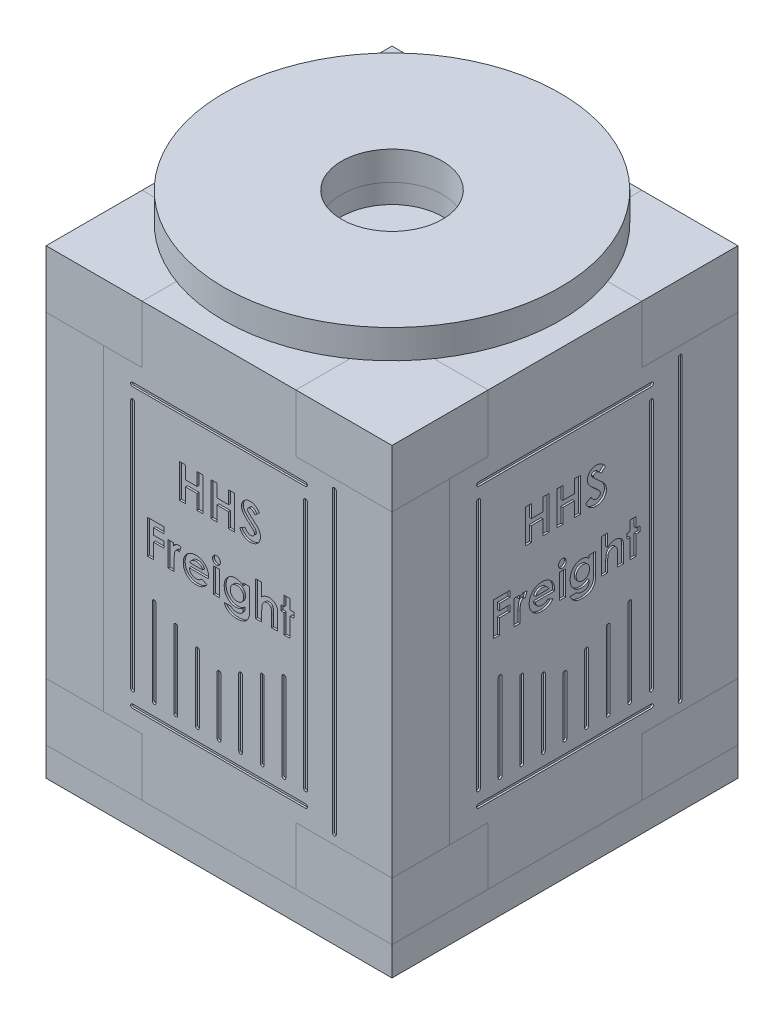
SolidWorks part; units mm, degrees
material "Cedar"
ref_plane "Front Plane" through (0, 0, 0) normal (0, 0, 1) x (1, 0, 0)
ref_plane "Top Plane" through (0, 0, 0) normal (0, 1, 0) x (1, 0, 0)
ref_plane "Right Plane" through (0, 0, 0) normal (1, 0, 0) x (0, 0, -1)
sketch "Sketch1" plane through (0, 0, 0) normal (0, 1, 0) x (1, 0, 0)
  line L0 (18, 8) -> (12, 8)
  line L1 (-18, -18) -> (18, -18)
  line L2 (-18, -18) -> (-18, 18)
  line L3 (-18, 18) -> (18, 18)
  line L4 (18, -18) -> (18, 18)
  line L5 (-18, -18) -> (18, 18) construction
  line L6 (-18, 18) -> (18, -18) construction
  line L7 (-8, 18) -> (8, 18)
  line L8 (-8, 18) -> (-8, 12)
  line L9 (-8, 12) -> (8, 12)
  line L10 (8, 18) -> (8, 12)
  line L11 (12, -8) -> (12, 8)
  line L12 (18, -8) -> (12, -8)
  line L13 (18, -8) -> (18, 8)
  line L14 (8, -18) -> (-8, -18)
  line L15 (8, -18) -> (8, -12)
  line L16 (8, -12) -> (-8, -12)
  line L17 (-8, -18) -> (-8, -12)
  line L18 (-18, -8) -> (-12, -8)
  line L19 (-12, 8) -> (-12, -8)
  line L20 (-18, 8) -> (-12, 8)
  line L21 (-18, 8) -> (-18, -8)
  circle A0 centre (0, 0) radius 16
  circle A1 centre (0, 0) radius 5.25
  dimension "D2" = 32
  dimension "D3" = 10.5
  dimension "D1" = 36
  dimension "D4" = 10
  dimension "D5" = 10
  dimension "D6" = 6
extrude "Boss-Extrude1" add sketch "Sketch1" along normal blind 6 contours A0 L9 L8 L3 L2 L20 L19 | A0 L19 L18 L2 L1 L17 L16 | L16 A0 L11 L9 L19 A1 | A0 L16 L15 L1 L4 L12 L11 | A0 L11 L0 L4 L3 L10 L9 | A1 region at (13.7273, 0, -13.7273) region at (12.9282, 0, -8.3919) region at (13.7273, 0, 13.7273) region at (-13.7273, 0, -13.7273) region at (-13.7273, 0, 13.7273) region at (0, 0, 0)
extrude "Boss-Extrude2" add sketch "Sketch1<3>" along normal blind 2 from offset 6 separate body contours A0 | A1
sketch "Sketch1<3>" plane through (0, 0, 0) normal (0, 1, 0) x (1, 0, 0) same geometry as "Sketch1"
sketch "Sketch2" plane through (0, 0, 12) normal (0, 0, 1) x (1, 0, 0)
  line L0 (8, 0) -> (18, 0) construction
  line L1 (18, 0) -> (18, 6) construction
  line L2 (18, 6) -> (8, 6) construction
  line L3 (8, 6) -> (8, 0) construction
  line L4 (-18, 0) -> (-8, 0) construction
  line L5 (-8, 0) -> (-8, 6) construction
  line L6 (-8, 6) -> (-18, 6) construction
  line L7 (-18, 6) -> (-18, 0) construction
  line L8 (8, 0) -> (18, 0)
  line L9 (18, 0) -> (18, 6)
  line L10 (18, 6) -> (8, 6)
  line L11 (8, 6) -> (8, 0)
  line L12 (-18, 0) -> (-8, 0)
  line L13 (-8, 0) -> (-8, 6)
  line L14 (-8, 6) -> (-18, 6)
  line L15 (-18, 6) -> (-18, 0)
  line L16 (-8, 6) -> (8, 6)
  line L17 (-12, 0) -> (-12, -33)
  line L18 (-12, -16.5) -> (18, -16.5) construction
  line L19 (18, 0) -> (18, -33)
  line L20 (-8, -39) -> (8, -39)
  line L21 (-18, -39) -> (-18, -33)
  line L22 (-8, -39) -> (-18, -39)
  line L23 (-8, -33) -> (-8, -39)
  line L24 (-18, -33) -> (-8, -33)
  line L25 (8, -39) -> (8, -33)
  line L26 (18, -39) -> (8, -39)
  line L27 (18, -33) -> (18, -39)
  line L28 (8, -33) -> (18, -33)
  line L29 (16, 8) -> (-16, 8) construction
  line M5 (-8, 0) -> (8, 0)
  line M6 (8, 0) -> (8, 6)
  line M8 (-8, 6) -> (-8, 0)
  dimension "D1" = 6
  dimension "D2" = 47
extrude "Boss-Extrude3" add sketch "Sketch2" along normal blind 6 separate body contours L18 L17 L24 L23 L20 L25 L28 L19 | L17 L18 L19 L8 L12 M5 | M8 M5 M6 region at (0, 3, 12) region at (3, -8.25, 12) region at (2.5127, -26.5774, 12)
sketch "Sketch4" plane through (0, 0, 18) normal (0, 0, 1) x (1, 0, 0)
  line L0 (12, -1) -> (12, -32) construction
  line L1 (-12, -33) -> (-8, -33) construction
  line L2 (-12, 0) -> (-8, 0) construction
  line L3 (12.2, -1) -> (12.2, -32)
  line L4 (11.8, -1) -> (11.8, -32)
  line L5 (-9, -2) -> (9, -2) construction
  line L6 (-9, -1.8) -> (9, -1.8)
  line L7 (-9, -2.2) -> (9, -2.2)
  line L8 (-9, -3.5) -> (-9, -29.5) construction
  line L9 (-8.8, -3.5) -> (-8.8, -29.5)
  line L10 (-9.2, -3.5) -> (-9.2, -29.5)
  line L11 (9, -3.5) -> (9, -29.5) construction
  line L12 (9.2, -3.5) -> (9.2, -29.5)
  line L13 (8.8, -3.5) -> (8.8, -29.5)
  line L14 (-9, -31) -> (9, -31) construction
  line L15 (-9, -30.8) -> (9, -30.8)
  line L16 (-9, -31.2) -> (9, -31.2)
  line L17 (-4.5, -21.5) -> (-4.5, -29.5) construction
  line L18 (-4.3, -21.5) -> (-4.3, -29.5)
  line L19 (-4.7, -21.5) -> (-4.7, -29.5)
  line L20 (0, -23.5) -> (0, -29.5) construction
  line L21 (0.2, -23.5) -> (0.2, -29.5)
  line L22 (-0.2, -23.5) -> (-0.2, -29.5)
  line L23 (4.5, -21.5) -> (4.5, -29.5) construction
  line L24 (4.7, -21.5) -> (4.7, -29.5)
  line L25 (4.3, -21.5) -> (4.3, -29.5)
  line L26 (-8.8, -10) -> (8.8, -10) construction
  line L27 (18, 0) -> (18, -33) construction
  line L28 (8, -33) -> (18, -33) construction
  line L29 (8, 0) -> (18, 0) construction
  line L30 (-12, 0) -> (-12, -33) construction
  line L31 (-9, -29.5) -> (-4.5, -29.5) construction
  line L32 (-4.5, -29.5) -> (0, -29.5) construction
  line L33 (0, -29.5) -> (4.5, -29.5) construction
  line L34 (4.5, -29.5) -> (9, -29.5) construction
  line L35 (-6.75, -29.5) -> (-6.75, -20.5) construction
  line L36 (-6.95, -29.5) -> (-6.95, -20.5)
  line L37 (-6.55, -29.5) -> (-6.55, -20.5)
  line L38 (-2.25, -29.5) -> (-2.25, -22.5) construction
  line L39 (-2.45, -29.5) -> (-2.45, -22.5)
  line L40 (-2.05, -29.5) -> (-2.05, -22.5)
  line L41 (2.25, -29.5) -> (2.25, -22.5) construction
  line L42 (2.05, -29.5) -> (2.05, -22.5)
  line L43 (2.45, -29.5) -> (2.45, -22.5)
  line L44 (6.75, -29.5) -> (6.75, -20.5) construction
  line L45 (6.55, -29.5) -> (6.55, -20.5)
  line L46 (6.95, -29.5) -> (6.95, -20.5)
  line L47 (-4.1282, -6.5) -> (-3.5, -6.5)
  line L48 (-3.5, -6.5) -> (-3.5, -7.8462)
  line L49 (-3.5, -7.8462) -> (-2.2885, -7.8462)
  line L50 (-2.2885, -7.8462) -> (-2.2885, -6.5)
  line L51 (-2.2885, -6.5) -> (-1.6603, -6.5)
  line L52 (-1.6603, -6.5) -> (-1.6603, -10)
  line L53 (-1.6603, -10) -> (-2.2885, -10)
  line L54 (-2.2885, -10) -> (-2.2885, -8.4744)
  line L55 (-2.2885, -8.4744) -> (-3.5, -8.4744)
  line L56 (-3.5, -8.4744) -> (-3.5, -10)
  line L57 (-3.5, -10) -> (-4.1282, -10)
  line L58 (-4.1282, -10) -> (-4.1282, -6.5)
  line L59 (-0.8526, -6.5) -> (-0.2244, -6.5)
  line L60 (-0.2244, -6.5) -> (-0.2244, -7.8462)
  line L61 (-0.2244, -7.8462) -> (0.9872, -7.8462)
  line L62 (0.9872, -7.8462) -> (0.9872, -6.5)
  line L63 (0.9872, -6.5) -> (1.6154, -6.5)
  line L64 (1.6154, -6.5) -> (1.6154, -10)
  line L65 (1.6154, -10) -> (0.9872, -10)
  line L66 (0.9872, -10) -> (0.9872, -8.4744)
  line L67 (0.9872, -8.4744) -> (-0.2244, -8.4744)
  line L68 (-0.2244, -8.4744) -> (-0.2244, -10)
  line L69 (-0.2244, -10) -> (-0.8526, -10)
  line L70 (-0.8526, -10) -> (-0.8526, -6.5)
  line L71 (4.2179, -6.9676) -> (3.7482, -7.3974)
  line L72 (2.1538, -9.3445) -> (2.7063, -9.0128)
  line L73 (-7.4487, -13.1987) -> (-5.7436, -13.1987)
  line L74 (-5.7436, -13.1987) -> (-5.7436, -13.8269)
  line L75 (-5.7436, -13.8269) -> (-6.8205, -13.8269)
  line L76 (-6.8205, -13.8269) -> (-6.8205, -14.5)
  line L77 (-6.8205, -14.5) -> (-5.7436, -14.5)
  line L78 (-5.7436, -14.5) -> (-5.7436, -15.1282)
  line L79 (-5.7436, -15.1282) -> (-6.8205, -15.1282)
  line L80 (-6.8205, -15.1282) -> (-6.8205, -16.6987)
  line L81 (-6.8205, -16.6987) -> (-7.4487, -16.6987)
  line L82 (-7.4487, -16.6987) -> (-7.4487, -13.1987)
  line L83 (-5.2949, -14.141) -> (-4.7564, -14.141)
  line L84 (-4.7564, -14.141) -> (-4.7564, -14.4558)
  line L85 (-3.9487, -14.1593) -> (-4.1436, -14.6914)
  line L86 (-4.6688, -15.5384) -> (-4.6667, -15.6632)
  line L87 (-4.6667, -15.6632) -> (-4.6667, -16.6987)
  line L88 (-4.6667, -16.6987) -> (-5.2949, -16.6987)
  line L89 (-5.2949, -16.6987) -> (-5.2949, -14.141)
  line L90 (-1.079, -15.5769) -> (-3.0962, -15.5769)
  line L91 (-1.7823, -15.9394) -> (-1.2564, -16.1897)
  line L92 (-1.0769, -15.4584) -> (-1.079, -15.5769)
  line L93 (-3.0513, -15.0833) -> (-1.7051, -15.0833)
  line L94 (-0.5833, -14.141) -> (0.0449, -14.141)
  line L95 (0.0449, -14.141) -> (0.0449, -16.6987)
  line L96 (0.0449, -16.6987) -> (-0.5833, -16.6987)
  line L97 (-0.5833, -16.6987) -> (-0.5833, -14.141)
  line L98 (2.5128, -14.141) -> (3.1859, -14.141)
  line L99 (3.1859, -14.141) -> (3.1859, -16.3229)
  line L100 (0.5357, -16.8782) -> (1.234, -16.8782)
  line L101 (2.5128, -14.4257) -> (2.5128, -14.141)
  line L102 (3.8141, -13.109) -> (4.4423, -13.109)
  line L103 (4.4423, -13.109) -> (4.4423, -14.418)
  line L104 (6.1026, -15.0216) -> (6.1026, -16.6987)
  line L105 (6.1026, -16.6987) -> (5.4744, -16.6987)
  line L106 (5.4744, -16.6987) -> (5.4744, -15.5867)
  line L107 (4.4423, -15.68) -> (4.4423, -16.6987)
  line L108 (4.4423, -16.6987) -> (3.8141, -16.6987)
  line L109 (3.8141, -16.6987) -> (3.8141, -13.109)
  line L110 (6.7756, -13.109) -> (7.4038, -13.109)
  line L111 (7.4038, -13.109) -> (7.4038, -14.141)
  line L112 (7.4038, -14.141) -> (7.8077, -14.141)
  line L113 (7.8077, -14.141) -> (7.8077, -14.6795)
  line L114 (7.8077, -14.6795) -> (7.4038, -14.6795)
  line L115 (7.4038, -14.6795) -> (7.4038, -16.6987)
  line L116 (7.4038, -16.6987) -> (6.7756, -16.6987)
  line L117 (6.7756, -16.6987) -> (6.7756, -14.6795)
  line L118 (6.7756, -14.6795) -> (6.4615, -14.6795)
  line L119 (6.4615, -14.6795) -> (6.4615, -14.141)
  line L120 (6.4615, -14.141) -> (6.7756, -14.141)
  line L121 (6.7756, -14.141) -> (6.7756, -13.109)
  arc A0 (12.2, -1) -> (11.8, -1) centre (12, -1) ccw
  arc A1 (11.8, -32) -> (12.2, -32) centre (12, -32) ccw
  arc A2 (-9, -1.8) -> (-9, -2.2) centre (-9, -2) ccw
  arc A3 (9, -2.2) -> (9, -1.8) centre (9, -2) ccw
  arc A4 (-8.8, -3.5) -> (-9.2, -3.5) centre (-9, -3.5) ccw
  arc A5 (-9.2, -29.5) -> (-8.8, -29.5) centre (-9, -29.5) ccw
  arc A6 (9.2, -3.5) -> (8.8, -3.5) centre (9, -3.5) ccw
  arc A7 (8.8, -29.5) -> (9.2, -29.5) centre (9, -29.5) ccw
  arc A8 (-9, -30.8) -> (-9, -31.2) centre (-9, -31) ccw
  arc A9 (9, -31.2) -> (9, -30.8) centre (9, -31) ccw
  arc A10 (-4.3, -21.5) -> (-4.7, -21.5) centre (-4.5, -21.5) ccw
  arc A11 (-4.7, -29.5) -> (-4.3, -29.5) centre (-4.5, -29.5) ccw
  arc A12 (0.2, -23.5) -> (-0.2, -23.5) centre (0, -23.5) ccw
  arc A13 (-0.2, -29.5) -> (0.2, -29.5) centre (0, -29.5) ccw
  arc A14 (4.7, -21.5) -> (4.3, -21.5) centre (4.5, -21.5) ccw
  arc A15 (4.3, -29.5) -> (4.7, -29.5) centre (4.5, -29.5) ccw
  arc A16 (-6.95, -29.5) -> (-6.55, -29.5) centre (-6.75, -29.5) ccw
  arc A17 (-6.55, -20.5) -> (-6.95, -20.5) centre (-6.75, -20.5) ccw
  arc A18 (-2.45, -29.5) -> (-2.05, -29.5) centre (-2.25, -29.5) ccw
  arc A19 (-2.05, -22.5) -> (-2.45, -22.5) centre (-2.25, -22.5) ccw
  arc A20 (2.05, -29.5) -> (2.45, -29.5) centre (2.25, -29.5) ccw
  arc A21 (2.45, -22.5) -> (2.05, -22.5) centre (2.25, -22.5) ccw
  arc A22 (6.55, -29.5) -> (6.95, -29.5) centre (6.75, -29.5) ccw
  arc A23 (6.95, -20.5) -> (6.55, -20.5) centre (6.75, -20.5) ccw
  spline S0 degree 3 poles (3.7482, -7.3974) (3.7106, -7.3423) (3.6515, -7.2661) (3.5645, -7.1794) (3.5019, -7.1281) (3.4384, -7.0881) (3.3546, -7.0509) (3.2883, -7.0383) (3.2448, -7.0385) knots 0 0 0 0 0.311824 0.448433 0.573381 0.689077 0.797573 1 1 1 1
  spline S1 degree 3 poles (3.2448, -7.0385) (3.2066, -7.0384) (3.1496, -7.0452) (3.0828, -7.0771) (3.0402, -7.1074) (3.0066, -7.1439) (2.9712, -7.194) (2.9619, -7.2389) (2.9615, -7.2677) knots 0 0 0 0 0.285993 0.416634 0.54738 0.671583 0.784401 1 1 1 1
  spline S2 degree 3 poles (2.9615, -7.2677) (2.9611, -7.2971) (2.9723, -7.3571) (3.0015, -7.4105) (3.0197, -7.4353) knots 0 0 0 0 0.487115 1 1 1 1
  spline S3 degree 3 poles (3.0197, -7.4353) (3.0376, -7.4592) (3.0725, -7.4967) (3.126, -7.5513) (3.1811, -7.6035) (3.2447, -7.6643) (3.3507, -7.7592) (3.435, -7.8345) (3.4951, -7.8868) knots 0 0 0 0 0.136349 0.233805 0.349411 0.483179 0.635967 1 1 1 1
  spline S4 degree 3 poles (3.4951, -7.8868) (3.5508, -7.9353) (3.6307, -8.0035) (3.7298, -8.091) (3.791, -8.145) (3.8427, -8.1917) (3.8936, -8.2392) (3.927, -8.2713) (3.9459, -8.2907) knots 0 0 0 0 0.366184 0.520457 0.655012 0.770624 0.865677 1 1 1 1
  spline S5 degree 3 poles (3.9459, -8.2907) (4.0062, -8.354) (4.0886, -8.4498) (4.1769, -8.5853) (4.2261, -8.682) (4.2632, -8.7795) (4.2987, -8.9155) (4.3078, -9.0218) (4.3077, -9.0934) knots 0 0 0 0 0.289954 0.417139 0.535255 0.648751 0.762405 1 1 1 1
  spline S6 degree 3 poles (4.3077, -9.0934) (4.3088, -9.1629) (4.2986, -9.2651) (4.2693, -9.3968) (4.2361, -9.4885) (4.1957, -9.5763) (4.1449, -9.6588) (4.0854, -9.7369) (4.0171, -9.8091) (3.9416, -9.8747) (3.8606, -9.933) (3.7733, -9.9812) (3.6805, -10.0209) (3.5823, -10.0514) (3.4413, -10.0823) (3.3313, -10.0899) (3.2567, -10.0897) knots 0 0 0 0 0.127927 0.189047 0.248544 0.307607 0.367248 0.426963 0.488617 0.550392 0.611331 0.672556 0.734024 0.797341 0.86225 1 1 1 1
  spline S7 degree 3 poles (3.2567, -10.0897) (3.1974, -10.0897) (3.1097, -10.0845) (2.9957, -10.0657) (2.9145, -10.0459) (2.8359, -10.0207) (2.7601, -9.9899) (2.6875, -9.9531) (2.6177, -9.9111) (2.5509, -9.8622) (2.4863, -9.8075) (2.4245, -9.7463) (2.3653, -9.6785) (2.309, -9.6041) (2.2337, -9.495) (2.1853, -9.4058) (2.1538, -9.3445) knots 0 0 0 0 0.125868 0.18624 0.244977 0.303358 0.36123 0.418489 0.475937 0.534204 0.594059 0.655469 0.718772 0.784975 0.853522 1 1 1 1
  spline S8 degree 3 poles (2.7063, -9.0128) (2.744, -9.0815) (2.8051, -9.1767) (2.9, -9.2858) (2.9711, -9.3495) (3.0445, -9.3995) (3.1449, -9.447) (3.2262, -9.4616) (3.2798, -9.4615) knots 0 0 0 0 0.307612 0.442139 0.566229 0.681222 0.789558 1 1 1 1
  spline S9 degree 3 poles (3.2798, -9.4615) (3.3326, -9.4619) (3.4104, -9.45) (3.5045, -9.4075) (3.5643, -9.3633) (3.6149, -9.3123) (3.6644, -9.2375) (3.6802, -9.1726) (3.6795, -9.1299) knots 0 0 0 0 0.275473 0.404346 0.53543 0.661427 0.777867 1 1 1 1
  spline S10 degree 3 poles (3.6795, -9.1299) (3.6794, -9.0892) (3.6671, -9.0273) (3.6317, -8.9488) (3.5999, -8.8993) (3.5674, -8.8579) (3.5364, -8.822) (3.4986, -8.7824) (3.4542, -8.7389) (3.4036, -8.6913) (3.3244, -8.6187) (3.2602, -8.564) (3.2153, -8.5262) knots 0 0 0 0 0.155091 0.238352 0.328404 0.379384 0.439618 0.509831 0.588875 0.677436 0.775547 1 1 1 1
  spline S11 degree 3 poles (3.2153, -8.5262) (3.1295, -8.4543) (3.0075, -8.3488) (2.8556, -8.2095) (2.7596, -8.1154) (2.6753, -8.0288) (2.6032, -7.9489) (2.5442, -7.8753) (2.482, -7.7881) (2.4231, -7.6818) (2.3559, -7.5146) (2.3324, -7.3839) (2.3333, -7.2979) knots 0 0 0 0 0.215201 0.309902 0.395959 0.473447 0.54214 0.602523 0.654726 0.747804 0.835278 1 1 1 1
  spline S12 degree 3 poles (2.3333, -7.2979) (2.333, -7.2388) (2.3418, -7.1512) (2.3689, -7.0383) (2.3978, -6.9579) (2.4354, -6.881) (2.4811, -6.8071) (2.5355, -6.737) (2.5968, -6.6706) (2.6644, -6.61) (2.7365, -6.5565) (2.813, -6.5113) (2.8932, -6.4739) (2.9776, -6.4452) (3.0967, -6.4176) (3.1894, -6.4106) (3.2518, -6.4103) knots 0 0 0 0 0.124457 0.184841 0.244567 0.304319 0.3652 0.427421 0.491262 0.555499 0.618605 0.680495 0.742473 0.804991 0.868252 1 1 1 1
  spline S13 degree 3 poles (3.2518, -6.4103) (3.334, -6.4103) (3.4572, -6.4257) (3.6153, -6.4753) (3.7109, -6.5198) (3.787, -6.563) (3.8453, -6.6028) (3.9046, -6.6483) (3.9654, -6.6998) (4.0266, -6.7582) (4.1135, -6.8458) (4.1765, -6.9173) (4.2179, -6.9676) knots 0 0 0 0 0.212977 0.319777 0.428556 0.485857 0.546559 0.611431 0.679821 0.753159 0.830753 1 1 1 1
  spline S14 degree 3 poles (-4.7564, -14.4558) (-4.728, -14.4007) (-4.6796, -14.3221) (-4.5939, -14.238) (-4.5252, -14.1864) (-4.4504, -14.1463) (-4.3448, -14.1077) (-4.2608, -14.0955) (-4.2046, -14.0962) knots 0 0 0 0 0.268422 0.393205 0.51643 0.637793 0.758061 1 1 1 1
  spline S15 degree 3 poles (-4.2046, -14.0962) (-4.1627, -14.0971) (-4.0739, -14.1067) (-3.9911, -14.1403) (-3.9487, -14.1593) knots 0 0 0 0 0.474168 1 1 1 1
  spline S16 degree 3 poles (-4.1436, -14.6914) (-4.1763, -14.6757) (-4.234, -14.6476) (-4.2971, -14.6349) (-4.3245, -14.6346) knots 0 0 0 0 0.570645 1 1 1 1
  spline S17 degree 3 poles (-4.3245, -14.6346) (-4.348, -14.6346) (-4.3839, -14.6398) (-4.4275, -14.6602) (-4.4598, -14.6796) (-4.4891, -14.7066) (-4.5183, -14.7379) (-4.5441, -14.7765) (-4.5713, -14.8195) (-4.5945, -14.8721) (-4.6144, -14.9349) (-4.6321, -15.0086) (-4.6443, -15.0937) (-4.656, -15.1892) (-4.6659, -15.3386) (-4.6693, -15.4563) (-4.6688, -15.5384) knots 0 0 0 0 0.066912 0.101141 0.136381 0.173598 0.214076 0.25798 0.305417 0.358685 0.420924 0.492691 0.574131 0.665182 0.766513 1 1 1 1
  spline S18 degree 3 poles (-3.0962, -15.5769) (-3.0887, -15.623) (-3.0744, -15.6909) (-3.044, -15.7764) (-3.0172, -15.8356) (-2.9863, -15.8915) (-2.9504, -15.9436) (-2.9097, -15.9919) (-2.8647, -16.0363) (-2.8159, -16.076) (-2.7637, -16.1108) (-2.7079, -16.1394) (-2.6494, -16.1635) (-2.5875, -16.1825) (-2.4987, -16.2004) (-2.4298, -16.2048) (-2.3831, -16.2051) knots 0 0 0 0 0.13403 0.198035 0.259813 0.320405 0.380626 0.441026 0.501202 0.561691 0.621161 0.680802 0.740903 0.802582 0.866186 1 1 1 1
  spline S19 degree 3 poles (-2.3831, -16.2051) (-2.3264, -16.2054) (-2.2425, -16.1967) (-2.1342, -16.1695) (-2.0573, -16.1397) (-1.983, -16.1026) (-1.8874, -16.04) (-1.8226, -15.982) (-1.7823, -15.9394) knots 0 0 0 0 0.25134 0.372249 0.494281 0.61618 0.739791 1 1 1 1
  spline S20 degree 3 poles (-1.2564, -16.1897) (-1.2885, -16.2355) (-1.3399, -16.3012) (-1.4152, -16.3812) (-1.4735, -16.4361) (-1.5342, -16.4861) (-1.5972, -16.532) (-1.6634, -16.5723) (-1.7314, -16.6092) (-1.8028, -16.6409) (-1.8772, -16.6679) (-1.9544, -16.6922) (-2.0354, -16.7108) (-2.1194, -16.7255) (-2.2378, -16.7398) (-2.3286, -16.7436) (-2.3901, -16.7436) knots 0 0 0 0 0.127328 0.18942 0.250008 0.309331 0.368387 0.427142 0.485687 0.544505 0.604586 0.665832 0.728669 0.793472 0.859914 1 1 1 1
  spline S21 degree 3 poles (-2.3901, -16.7436) (-2.4844, -16.7437) (-2.6237, -16.7336) (-2.8019, -16.6932) (-2.9265, -16.653) (-3.0439, -16.5998) (-3.1543, -16.5348) (-3.2587, -16.4592) (-3.354, -16.3713) (-3.4409, -16.2758) (-3.5171, -16.1731) (-3.5809, -16.0641) (-3.6333, -15.9495) (-3.674, -15.8289) (-3.714, -15.6577) (-3.7246, -15.524) (-3.7244, -15.4339) knots 0 0 0 0 0.135079 0.198876 0.261192 0.322136 0.383017 0.444315 0.506363 0.568185 0.628944 0.689079 0.748666 0.809078 0.870918 1 1 1 1
  spline S22 degree 3 poles (-3.7244, -15.4339) (-3.7244, -15.3414) (-3.7143, -15.2047) (-3.6739, -15.0296) (-3.6331, -14.9063) (-3.5815, -14.7887) (-3.5169, -14.6778) (-3.4409, -14.5732) (-3.3544, -14.4753) (-3.2587, -14.387) (-3.157, -14.3083) (-3.0481, -14.2428) (-2.9334, -14.1897) (-2.8135, -14.1467) (-2.6423, -14.1077) (-2.5092, -14.0951) (-2.4189, -14.0962) knots 0 0 0 0 0.132706 0.195663 0.257481 0.318729 0.379576 0.441281 0.50399 0.566629 0.62786 0.688183 0.748487 0.808936 0.870587 1 1 1 1
  spline S23 degree 3 poles (-2.4189, -14.0962) (-2.3239, -14.0962) (-2.1836, -14.106) (-2.0043, -14.1467) (-1.8788, -14.1865) (-1.7614, -14.241) (-1.6494, -14.3044) (-1.5456, -14.3817) (-1.4489, -14.4691) (-1.3616, -14.566) (-1.2853, -14.6714) (-1.2204, -14.784) (-1.1677, -14.9045) (-1.1271, -15.0324) (-1.0869, -15.2165) (-1.0768, -15.3606) (-1.0769, -15.4584) knots 0 0 0 0 0.132529 0.19498 0.255982 0.315768 0.37518 0.435072 0.495743 0.556656 0.616619 0.676758 0.737601 0.799533 0.863575 1 1 1 1
  spline S24 degree 3 poles (-1.7051, -15.0833) (-1.7264, -15.0194) (-1.7703, -14.925) (-1.8645, -14.824) (-1.9466, -14.7567) (-2.0405, -14.7021) (-2.1794, -14.6484) (-2.2921, -14.6347) (-2.3677, -14.6346) knots 0 0 0 0 0.237159 0.356489 0.480961 0.607829 0.735017 1 1 1 1
  spline S25 degree 3 poles (-2.3677, -14.6346) (-2.4502, -14.6335) (-2.6121, -14.6569) (-2.7596, -14.7276) (-2.8234, -14.7748) knots 0 0 0 0 0.510296 1 1 1 1
  spline S26 degree 3 poles (-2.8234, -14.7748) (-2.8697, -14.8079) (-2.9576, -14.904) (-3.0205, -15.0177) (-3.0513, -15.0833) knots 0 0 0 0 0.437897 1 1 1 1
  spline S27 degree 3 poles (-0.2706, -13.0641) (-0.2175, -13.0632) (-0.1378, -13.0797) (-0.0443, -13.1334) (0.0175, -13.1881) (0.0688, -13.2535) (0.1219, -13.3521) (0.1336, -13.4369) (0.1346, -13.4925) knots 0 0 0 0 0.242963 0.363855 0.490606 0.61874 0.7433 1 1 1 1
  spline S28 degree 3 poles (0.1346, -13.4925) (0.1342, -13.5477) (0.1209, -13.6309) (0.0699, -13.7295) (0.0181, -13.7939) (-0.043, -13.8477) (-0.1344, -13.9023) (-0.2136, -13.9166) (-0.2657, -13.9167) knots 0 0 0 0 0.256469 0.381955 0.510704 0.637377 0.757775 1 1 1 1
  spline S29 degree 3 poles (-0.2657, -13.9167) (-0.3194, -13.9176) (-0.3995, -13.9009) (-0.4943, -13.8476) (-0.5558, -13.7918) (-0.6078, -13.7259) (-0.6587, -13.6249) (-0.6732, -13.5401) (-0.6731, -13.4834) knots 0 0 0 0 0.242759 0.363443 0.489711 0.617482 0.74228 1 1 1 1
  spline S30 degree 3 poles (-0.6731, -13.4834) (-0.6722, -13.4288) (-0.6599, -13.3461) (-0.6081, -13.2493) (-0.5571, -13.1851) (-0.4958, -13.1314) (-0.4024, -13.0793) (-0.3234, -13.0637) (-0.2706, -13.0641) knots 0 0 0 0 0.255027 0.378937 0.506523 0.634371 0.754976 1 1 1 1
  spline S31 degree 3 poles (3.1859, -16.3229) (3.1855, -16.4235) (3.1793, -16.57) (3.1517, -16.7569) (3.1232, -16.8818) (3.0862, -16.9956) (3.0277, -17.1303) (2.9696, -17.2208) (2.9244, -17.2736) knots 0 0 0 0 0.300234 0.436257 0.562885 0.681681 0.792784 1 1 1 1
  spline S32 degree 3 poles (2.9244, -17.2736) (2.8668, -17.3421) (2.7661, -17.4331) (2.6111, -17.5277) (2.4833, -17.5862) (2.3444, -17.6306) (2.1387, -17.6749) (1.9766, -17.6862) (1.8657, -17.6859) knots 0 0 0 0 0.228421 0.343997 0.462956 0.586703 0.716303 1 1 1 1
  spline S33 degree 3 poles (1.8657, -17.6859) (1.7497, -17.686) (1.5819, -17.677) (1.3706, -17.6366) (1.2329, -17.596) (1.108, -17.5434) (0.9936, -17.4804) (0.8899, -17.4051) (0.7954, -17.3205) (0.7123, -17.2246) (0.6162, -17.0813) (0.5631, -16.9616) (0.5357, -16.8782) knots 0 0 0 0 0.207411 0.299345 0.383942 0.46371 0.541137 0.616855 0.692287 0.767513 0.843065 1 1 1 1
  spline S34 degree 3 poles (1.234, -16.8782) (1.265, -16.9152) (1.3194, -16.9647) (1.4036, -17.0159) (1.4737, -17.0477) (1.5508, -17.0719) (1.6656, -17.0973) (1.7567, -17.1022) (1.8187, -17.1026) knots 0 0 0 0 0.223655 0.337943 0.455777 0.579824 0.711809 1 1 1 1
  spline S35 degree 3 poles (1.8187, -17.1026) (1.896, -17.1032) (2.0065, -17.0942) (2.1437, -17.0609) (2.2283, -17.0254) (2.3013, -16.9828) (2.3622, -16.9332) (2.4124, -16.8786) (2.4453, -16.8272) (2.4649, -16.7806) (2.4782, -16.7404) (2.4883, -16.694) (2.4975, -16.6424) (2.5043, -16.5848) (2.5108, -16.4967) (2.5137, -16.4277) (2.5128, -16.3797) knots 0 0 0 0 0.197721 0.282266 0.359994 0.431569 0.49787 0.56009 0.620807 0.652682 0.689174 0.72906 0.773983 0.823375 0.87735 1 1 1 1
  spline S36 degree 3 poles (2.5128, -16.3797) (2.4605, -16.4336) (2.3773, -16.5063) (2.2551, -16.5821) (2.1633, -16.6262) (2.0671, -16.6585) (1.9292, -16.6903) (1.8209, -16.6983) (1.7472, -16.6987) knots 0 0 0 0 0.263928 0.385524 0.503705 0.620733 0.741155 1 1 1 1
  spline S37 degree 3 poles (1.7472, -16.6987) (1.6654, -16.6993) (1.5439, -16.6877) (1.3881, -16.6489) (1.2773, -16.6091) (1.1723, -16.5563) (1.0714, -16.4934) (0.9766, -16.4172) (0.8866, -16.3319) (0.8052, -16.2372) (0.7336, -16.1354) (0.6732, -16.0273) (0.6242, -15.9129) (0.5851, -15.7929) (0.5484, -15.6213) (0.5388, -15.4878) (0.5385, -15.3974) knots 0 0 0 0 0.1237 0.183445 0.242476 0.301273 0.360988 0.421869 0.484864 0.548268 0.610431 0.67277 0.73514 0.798288 0.86338 1 1 1 1
  spline S38 degree 3 poles (0.5385, -15.3974) (0.5379, -15.3014) (0.5491, -15.1601) (0.5879, -14.9788) (0.6283, -14.8529) (0.6815, -14.7349) (0.7672, -14.587) (0.8481, -14.4869) (0.9094, -14.4271) knots 0 0 0 0 0.269734 0.396745 0.520319 0.640547 0.759724 1 1 1 1
  spline S39 degree 3 poles (0.9094, -14.4271) (0.9635, -14.3733) (1.0511, -14.3012) (1.1787, -14.2236) (1.2775, -14.1773) (1.3803, -14.1405) (1.5246, -14.1055) (1.6367, -14.0959) (1.7121, -14.0962) knots 0 0 0 0 0.256681 0.379784 0.501471 0.623319 0.746312 1 1 1 1
  spline S40 degree 3 poles (1.7121, -14.0962) (1.783, -14.0968) (1.8891, -14.1046) (2.0257, -14.1381) (2.1253, -14.1722) (2.2237, -14.2164) (2.3574, -14.296) (2.4519, -14.3702) (2.5128, -14.4257) knots 0 0 0 0 0.2398 0.357658 0.474596 0.595177 0.721609 1 1 1 1
  spline S41 degree 3 poles (1.8622, -14.6795) (1.8139, -14.6805) (1.7421, -14.6847) (1.6508, -14.7072) (1.5861, -14.7287) (1.5251, -14.7576) (1.4675, -14.793) (1.4127, -14.8339) (1.3625, -14.8814) (1.3159, -14.9326) (1.2767, -14.989) (1.2419, -15.0474) (1.2148, -15.11) (1.1924, -15.1753) (1.1736, -15.269) (1.1653, -15.3412) (1.1667, -15.3904) knots 0 0 0 0 0.130325 0.192491 0.253031 0.313597 0.374077 0.434784 0.49761 0.560052 0.621032 0.682272 0.742887 0.804621 0.867736 1 1 1 1
  spline S42 degree 3 poles (1.1667, -15.3904) (1.1657, -15.4415) (1.1728, -15.5162) (1.1933, -15.6128) (1.2159, -15.6798) (1.2443, -15.7437) (1.2783, -15.8043) (1.3203, -15.8603) (1.367, -15.9129) (1.4187, -15.9604) (1.4742, -16.0017) (1.5326, -16.0374) (1.5951, -16.0653) (1.6602, -16.0878) (1.7529, -16.11) (1.8254, -16.1144) (1.8741, -16.1154) knots 0 0 0 0 0.134675 0.197932 0.260448 0.321294 0.382443 0.443854 0.505984 0.568072 0.628986 0.688849 0.748568 0.809329 0.870916 1 1 1 1
  spline S43 degree 3 poles (1.8741, -16.1154) (1.9219, -16.1163) (1.9921, -16.1093) (2.0823, -16.0885) (2.1456, -16.0669) (2.2054, -16.0385) (2.2623, -16.0047) (2.3153, -15.9638) (2.3653, -15.9175) (2.4104, -15.8661) (2.4502, -15.8104) (2.4829, -15.7503) (2.5108, -15.6869) (2.5314, -15.6193) (2.5528, -15.5225) (2.5578, -15.4467) (2.5577, -15.3953) knots 0 0 0 0 0.128347 0.189068 0.248938 0.308024 0.366703 0.426834 0.487805 0.549753 0.610659 0.671749 0.733442 0.796702 0.861717 1 1 1 1
  spline S44 degree 3 poles (2.5577, -15.3953) (2.5579, -15.3447) (2.5527, -15.2699) (2.5315, -15.1741) (2.5106, -15.1071) (2.4833, -15.0437) (2.4491, -14.9846) (2.41, -14.9287) (2.364, -14.8779) (2.3144, -14.8309) (2.2597, -14.7911) (2.2027, -14.756) (2.1413, -14.7281) (2.0765, -14.7062) (1.9836, -14.6856) (1.9113, -14.6785) (1.8622, -14.6795) knots 0 0 0 0 0.135592 0.199609 0.261895 0.32322 0.383708 0.44425 0.505361 0.566852 0.626748 0.685936 0.745803 0.8065 0.868686 1 1 1 1
  spline S45 degree 3 poles (4.4423, -14.418) (4.503, -14.3667) (4.597, -14.297) (4.729, -14.221) (4.8264, -14.1757) (4.9242, -14.1404) (5.0548, -14.1068) (5.1548, -14.0956) (5.2213, -14.0962) knots 0 0 0 0 0.277052 0.406612 0.530555 0.650913 0.768693 1 1 1 1
  spline S46 degree 3 poles (5.2213, -14.0962) (5.2836, -14.0966) (5.3762, -14.1032) (5.4949, -14.1312) (5.5791, -14.1595) (5.6589, -14.1976) (5.7621, -14.2575) (5.8315, -14.3156) (5.8747, -14.3577) knots 0 0 0 0 0.259226 0.382754 0.505762 0.626832 0.749442 1 1 1 1
  spline S47 degree 3 poles (5.8747, -14.3577) (5.9131, -14.3953) (5.9632, -14.46) (6.0154, -14.5571) (6.0477, -14.6373) (6.0717, -14.7242) (6.0974, -14.8521) (6.1021, -14.9528) (6.1026, -15.0216) knots 0 0 0 0 0.223433 0.33833 0.457908 0.582303 0.71317 1 1 1 1
  spline S48 degree 3 poles (5.4744, -15.5867) (5.4743, -15.5192) (5.4733, -15.4222) (5.4685, -15.2988) (5.4638, -15.2195) (5.4573, -15.1494) (5.4508, -15.088) (5.4418, -15.0356) (5.4283, -14.9786) (5.4063, -14.9177) (5.3743, -14.8527) (5.3316, -14.7991) (5.2822, -14.7549) (5.225, -14.7212) (5.1388, -14.6869) (5.0673, -14.6801) (5.0193, -14.6795) knots 0 0 0 0 0.174837 0.251114 0.319598 0.380332 0.433305 0.479348 0.517934 0.584706 0.64666 0.704382 0.760946 0.817379 0.875229 1 1 1 1
  spline S49 degree 3 poles (5.0193, -14.6795) (4.9555, -14.6785) (4.8605, -14.6945) (4.7464, -14.7497) (4.6699, -14.8061) (4.6033, -14.8767) (4.5265, -14.9901) (4.489, -15.0885) (4.4718, -15.1577) knots 0 0 0 0 0.243247 0.359969 0.480398 0.603252 0.728258 1 1 1 1
  spline S50 degree 3 poles (4.4718, -15.1577) (4.4649, -15.1824) (4.4603, -15.225) (4.4525, -15.2877) (4.4501, -15.3484) (4.4459, -15.4182) (4.4437, -15.5297) (4.4424, -15.618) (4.4423, -15.68) knots 0 0 0 0 0.146619 0.244884 0.361489 0.494127 0.645383 1 1 1 1
  point P2 (12, -16.5)
  point P7 (0, -2)
  point P14 (-9, -16.5)
  point P21 (9, -16.5)
  point P28 (0, -31)
  point P35 (-4.5, -25.5)
  point P42 (0, -26.5)
  point P49 (4.5, -25.5)
  point P72 (-6.75, -25)
  point P82 (-2.25, -26)
  point P91 (2.25, -26)
  point P98 (6.75, -25)
  dimension "D1" = 6
  dimension "D2" = 0.2
  dimension "D3" = 1
  dimension "D4" = 1
  dimension "D5" = 3
  dimension "D6" = 3
  dimension "D7" = 1.5
  dimension "D8" = 1.5
  dimension "D9" = 2
  dimension "D10" = 2
  dimension "D11" = 8
  dimension "D12" = 6
  dimension "D13" = 8
  dimension "D14" = 7
  dimension "D15" = 7
  dimension "D16" = 9
  dimension "D17" = 9
  dimension "D18" = 8
extrude "Cut-Extrude1" cut sketch "Sketch4" against normal blind 0.2
pattern_circular "CirPattern1" count 4 over 360 about axis through (0, 8, 0) along (0, -1, 0) reverse direction yes of bodies 109 103
extrude "Boss-Extrude4" add sketch "Sketch1<4>" along normal blind 6 from offset 39 separate body contours A0 L0 L4 L3 L10 | L15 A0 L12 L11 L0 L10 L9 L8 L20 L19 L18 L17 L16 A1 | A0 L8 L3 L2 L20 | A0 L18 L2 L1 L17 | A0 L15 L1 L4 L12 | A1 region at (13.7273, 0, -13.7273) region at (12.9282, 0, -8.3919) region at (13.7273, 0, 13.7273) region at (-13.7273, 0, -13.7273) region at (-13.7273, 0, 13.7273) region at (0, 0, 0) offset against normal yes
sketch "Sketch1<4>" plane through (0, 0, 0) normal (0, 1, 0) x (1, 0, 0) same geometry as "Sketch1"
sketch "Sketch3" plane through (0, -39, 0) normal (0, -1, 0) x (1, 0, 0)
  line L1 (-18, 18) -> (18, 18)
  line L2 (-18, 18) -> (-18, -18)
  line L3 (-18, -18) -> (18, -18)
  line L4 (18, 18) -> (18, -18)
  circle A0 centre (0, 0) radius 17
  circle A1 centre (0, 0) radius 16 construction
  dimension "D1" = 1
extrude "Boss-Extrude5" add sketch "Sketch3" along normal blind 3 separate body
sketch "Sketch5" plane through (0, 8, 0) normal (0, 1, 0) x (1, 0, 0)
  circle A0 centre (0, 0) radius 10
  circle A1 centre (0, 0) radius 25.4558
  dimension "D1" = 20
extrude "Cut-Extrude2" cut sketch "Sketch5" against normal through all
sketch "Sketch6" plane through (0, 8, 0) normal (0, 1, 0) x (1, 0, 0)
  circle A0 centre (0, 0) radius 17.5
  circle A1 centre (0, 0) radius 5.25 construction
  circle A2 centre (0, 0) radius 5.25
  dimension "D1" = 35
extrude "Boss-Extrude6" add sketch "Sketch6" along normal blind 3 separate body
